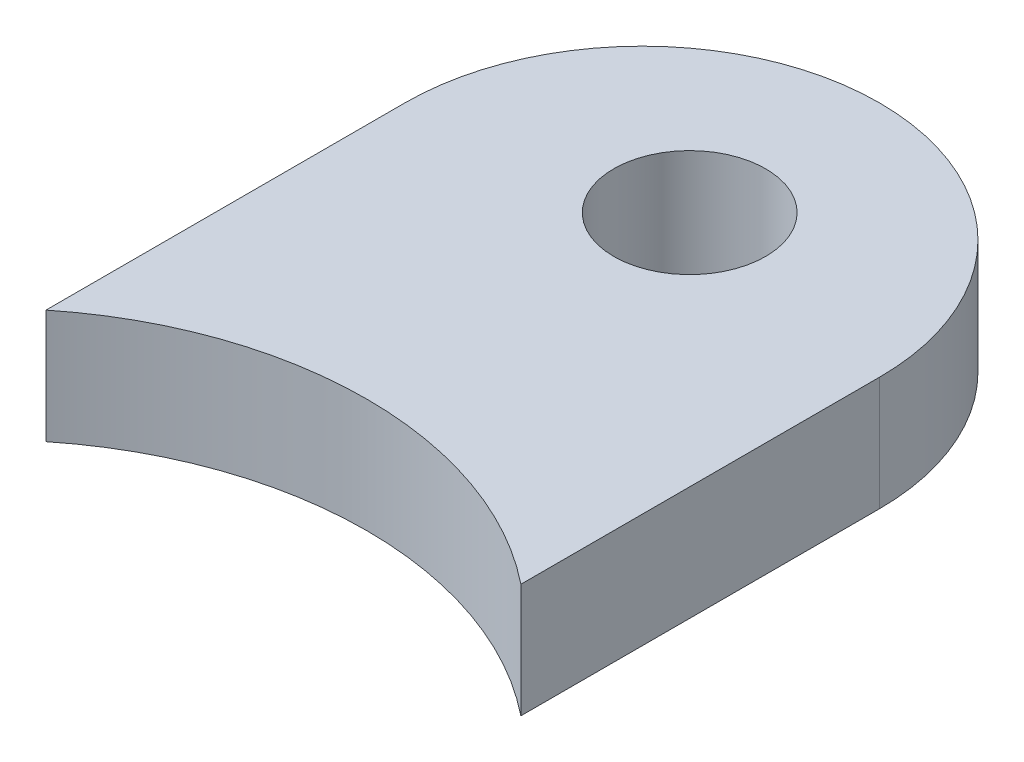
SolidWorks part; units mm, degrees
ref_plane "Front Plane" through (0, 0, 0) normal (0, 0, 1) x (1, 0, 0)
ref_plane "Top Plane" through (0, 0, 0) normal (0, 1, 0) x (1, 0, 0)
ref_plane "Right Plane" through (0, 0, 0) normal (1, 0, 0) x (0, 0, -1)
sketch "Sketch1" plane through (0, 0, 0) normal (0, 1, 0) x (1, 0, 0)
  line L0 (12.5, 35) -> (12.5, 0) construction
  line L1 (0, 0) -> (25, 0)
  line L2 (0, 0) -> (0, 35)
  line L3 (0, 35) -> (25, 35)
  line L4 (25, 0) -> (25, 35)
  circle A0 centre (12.5, 25) radius 4
  dimension "D3" = 8
  dimension "D1" = 25
  dimension "D2" = 35
  dimension "D4" = 10
extrude "Boss-Extrude1" add sketch "Sketch1" along normal blind 6
fillet "Fillet1" radius 12.5 2 edges at (25, 3, -35) (0, 3, -35)
sketch "Sketch2" plane through (0, 6, 0) normal (0, 1, 0) x (1, 0, 0)
  line L0 (12.5, 0) -> (12.5, -12) construction
  line L1 (0, 0) -> (25, 0) construction
  circle A0 centre (12.5, -12) radius 20
  dimension "D1" = 40
  dimension "D2" = 12
extrude "Cut-Extrude1" cut sketch "Sketch2" against normal blind 6
